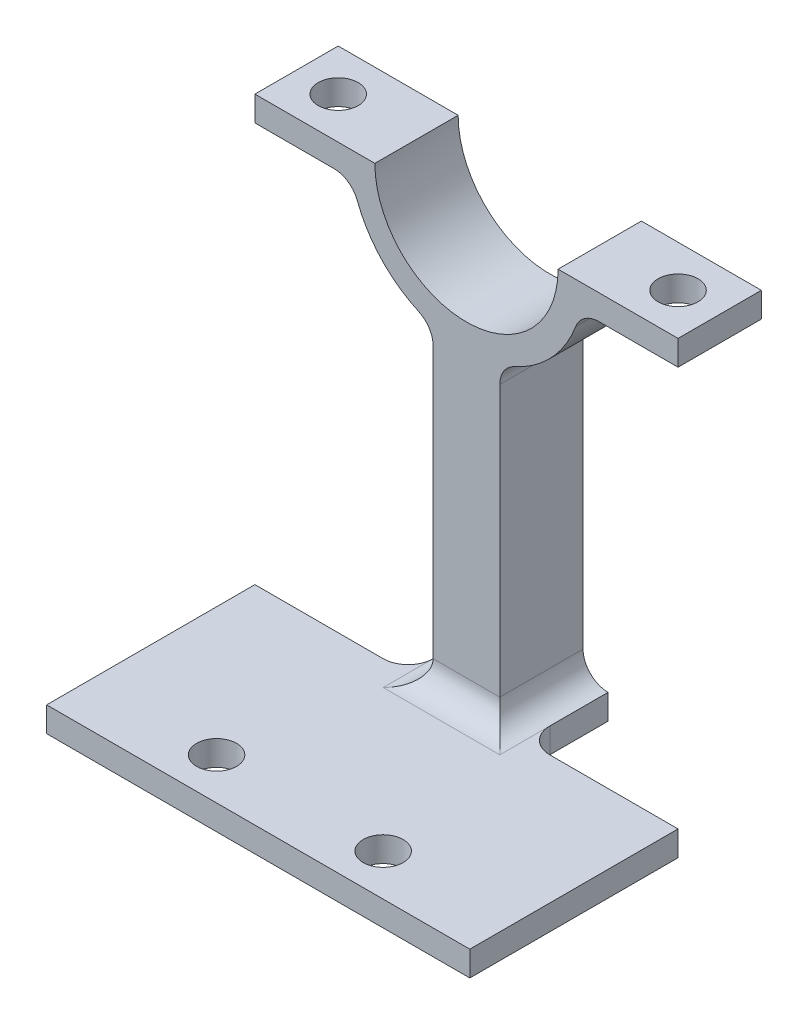
SolidWorks part; units mm, degrees
material "Windform GT"
ref_plane "Front Plane" through (0, 0, 0) normal (0, 0, 1) x (1, 0, 0)
ref_plane "Top Plane" through (0, 0, 0) normal (0, 1, 0) x (1, 0, 0)
ref_plane "Right Plane" through (0, 0, 0) normal (1, 0, 0) x (0, 0, -1)
sketch "Sketch1" plane through (0, 0, 0) normal (0, 0, 1) x (1, 0, 0)
  line L0 (5.5, 0) -> (12.7, 0)
  line L1 (12.7, 0) -> (12.7, -1.5)
  line L2 (12.7, -1.5) -> (6.8374, -1.5)
  line L5 (0, 0) -> (0, -7) construction
  line L7 (-12.7, -1.5) -> (-6.8374, -1.5)
  line L8 (-12.7, 0) -> (-12.7, -1.5)
  line L9 (-5.5, 0) -> (-12.7, 0)
  arc A2 (5.5, 0) -> (-5.5, 0) centre (0, 0) cw
  arc A3 (-6.8374, -1.5) -> (6.8374, -1.5) centre (0, 0) ccw
  point P2 (-6.3246, -1.7147)
  point P3 (0, -6.5)
  dimension "D1" = 7
  dimension "D2" = 5.5
  dimension "D3" = 12.7
  dimension "D4" = 1.5
extrude "Boss-Extrude1" add sketch "Sketch1" along normal mid plane 5
sketch "Sketch2" plane through (0, 0, 0) normal (0, 1, 0) x (1, 0, 0)
  line L0 (12.7, 0) -> (-12.7, 0) construction
  line L1 (-12.7, -2.5) -> (-12.7, 2.5) construction
  line L2 (0, 0) -> (0, 2.5) construction
  line L3 (5.5, 2.5) -> (-5.5, 2.5) construction
  circle A0 centre (-10.2, 0) radius 1.2
  circle A1 centre (10.2, 0) radius 1.2
  dimension "D1" = 2.5
  dimension "D2" = 2.4
extrude "Cut-Extrude1" cut sketch "Sketch2" against normal through all
sketch "Sketch6" plane through (0, 0, 0) normal (0, 1, 0) x (1, 0, 0)
  line L0 (-5.5, -2.5) -> (-5.5, 2.5) construction
  line L1 (2, 2.5) -> (-2, 2.5)
  line L2 (2, 2.5) -> (2, -2.5)
  line L3 (2, -2.5) -> (-2, -2.5)
  line L4 (-2, 2.5) -> (-2, -2.5)
  line L5 (2, 2.5) -> (-2, -2.5) construction
  line L6 (2, -2.5) -> (-2, 2.5) construction
  point P0 (0, 0)
  dimension "D1" = 4
extrude "Boss-Extrude2" add sketch "Sketch6" along normal up to surface (18.7918 mm away) from offset 25.5 up to face at (0, -4.25, 0) offset against normal yes
sketch "Sketch7" plane through (0, -25.5, 0) normal (0, -1, 0) x (1, 0, 0)
  line L0 (0, 0) -> (0, 15) construction
  line L13 (0, 0) -> (0, -2.5) construction
  line L18 (2, -2.5) -> (-2, -2.5) construction
  line L19 (3.5, -2.5) -> (-3.5, -2.5)
  line L20 (-6.8374, -2.5) -> (-2, -2.5) construction
  line L24 (-3.5, -2.5) -> (-3.5, 2.5)
  line L25 (-2, 2.5) -> (-6.8374, 2.5) construction
  line L27 (-3.5, 2.5) -> (-12.7, 2.5)
  line L29 (-12.7, 2.5) -> (-12.7, 15)
  line L30 (-12.7, 15) -> (12.7, 15)
  line L31 (12.7, 2.5) -> (12.7, 15)
  line L32 (3.5, 2.5) -> (12.7, 2.5)
  line L33 (3.5, -2.5) -> (3.5, 2.5)
  point P2 (0, 18.0878)
  dimension "D1" = 7
  dimension "D2" = 12.5
extrude "Boss-Extrude4" add sketch "Sketch7" along normal blind 1.5
fillet "Fillet1" radius 1.5 9 edges at (2, -25.5, 0) (-2, -25.5, 0) (-6.8374, -1.5, 0) (-2, -6.7082, 0) (2, -6.7082, 0) (6.8374, -1.5, 0) (3.5, -26.25, 2.5) (-3.5, -26.25, 2.5) (0, -25.5, 2.5)
sketch "Sketch8" plane through (0, 0, 0) normal (0, 1, 0) x (1, 0, 0)
  line L0 (0, 2.5) -> (0, -15) construction
  line L1 (12.7, -15) -> (-12.7, -15) construction
  line L2 (-5, 2.5) -> (-5, -15) construction
  line L3 (5, 2.5) -> (5, -15) construction
  line L4 (5.5, 2.5) -> (-5.5, 2.5) construction
  line L5 (-5.5, 2.5) -> (-12.7, 2.5) construction
  circle A0 centre (-5, -12.5) radius 1.2
  circle A3 centre (5, -12.5) radius 1.2
  point P18 (0, 0)
  point P19 (-8.4384, 2.5)
  dimension "D2" = 2.4
  dimension "D1" = 2.5
  dimension "D4" = 5
extrude "Cut-Extrude3" cut sketch "Sketch8" against normal through all
